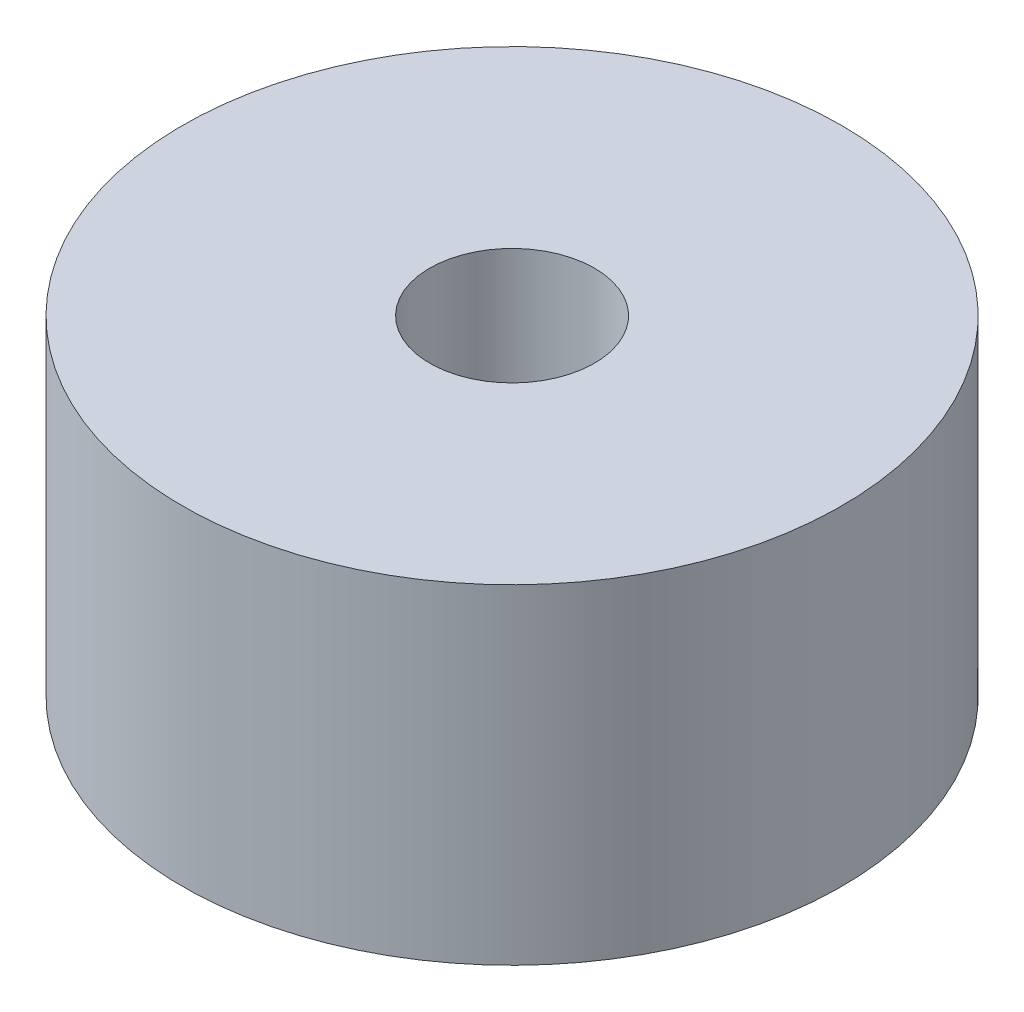
SolidWorks part; units mm, degrees
ref_plane "Front Plane" through (0, 0, 0) normal (0, 0, 1) x (1, 0, 0)
ref_plane "Top Plane" through (0, 0, 0) normal (0, 1, 0) x (1, 0, 0)
ref_plane "Right Plane" through (0, 0, 0) normal (1, 0, 0) x (0, 0, -1)
sketch "Sketch2" plane through (0, 0, 0) normal (0, 1, 0) x (1, 0, 0)
  circle A0 centre (0, 0) radius 4.7625
  circle A1 centre (0, 0) radius 19.05
  dimension "D1" = 9.525
  dimension "D2" = 38.1
extrude "Boss-Extrude1" add sketch "Sketch2" along normal blind 19.05
